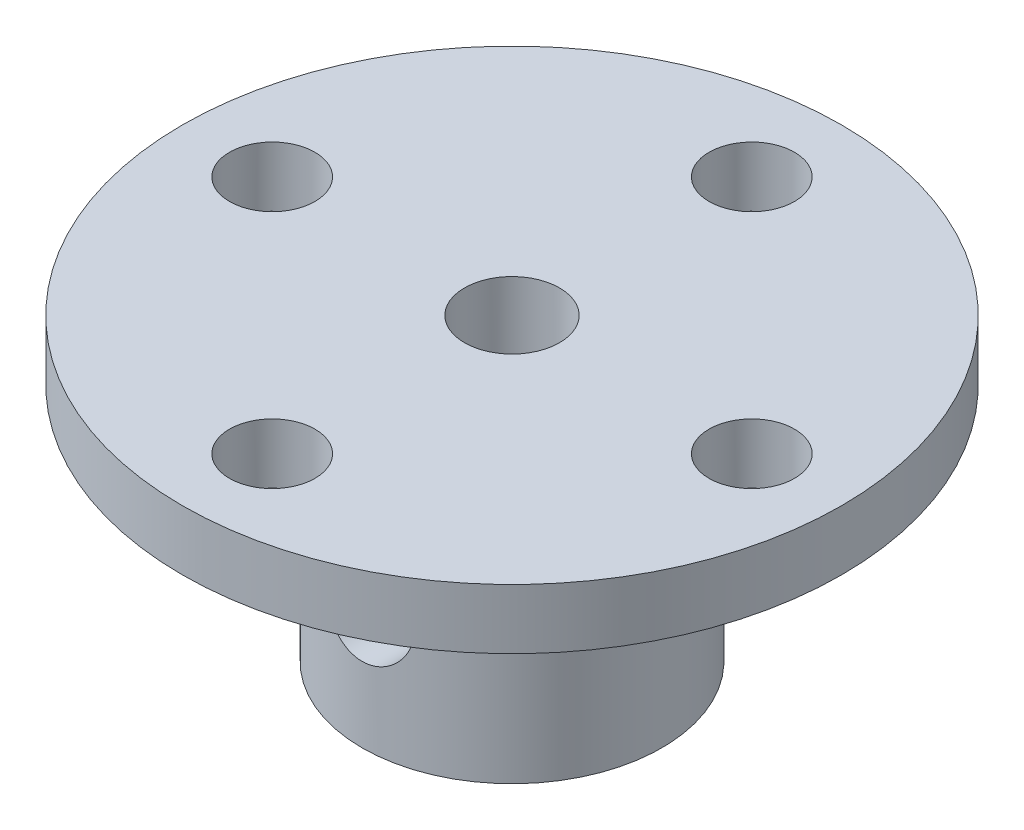
SolidWorks part; units mm, degrees
ref_plane "Front Plane" through (0, 0, 0) normal (0, 0, 1) x (1, 0, 0)
ref_plane "Top Plane" through (0, 0, 0) normal (0, 1, 0) x (1, 0, 0)
ref_plane "Right Plane" through (0, 0, 0) normal (1, 0, 0) x (0, 0, -1)
sketch "Sketch1" plane through (0, 0, 0) normal (0, 1, 0) x (1, 0, 0)
  circle A0 centre (0, 0) radius 11
  dimension "D1" = 22
extrude "Boss-Extrude1" add sketch "Sketch1" along normal blind 2
sketch "Sketch2" plane through (0, 0, 0) normal (0, 1, 0) x (1, 0, 0)
  circle A0 centre (0, 0) radius 5
  dimension "D1" = 10
extrude "Boss-Extrude2" add sketch "Sketch2" against normal blind 8
sketch "Sketch3" plane through (0, 2, 0) normal (0, -1, 0) x (-1, 0, 0)
  circle A0 centre (0, 0) radius 1.585
  dimension "D1" = 3.17
extrude "Cut-Extrude1" cut sketch "Sketch3" along normal through all
sketch "Sketch4" plane through (0, 2, 0) normal (0, 1, 0) x (1, 0, 0)
  circle A0 centre (0, 8) radius 1.425
  dimension "D1" = 2.85
  dimension "D2" = 8
extrude "Cut-Extrude2" cut sketch "Sketch4" against normal up to next
pattern_circular "CirPattern1" count 4 over 360 about axis through (0, 2, 0) along (0, 1, 0) of "Cut-Extrude2"
sketch "Sketch5" plane through (0, 0, 0) normal (0, 0, 1) x (1, 0, 0)
  line L3 (-5, -4) -> (5, -4) construction
  line L4 (-5, 0) -> (-5, -8) construction
  line L5 (5, -8) -> (5, 0) construction
  line L6 (0, 0) -> (0, -8) construction
  line L7 (-5, -8) -> (5, -8) construction
  circle A0 centre (0, -4) radius 1.5
  point P13 (0, -4)
  dimension "D1" = 3
extrude "Cut-Extrude3" cut sketch "Sketch5" against normal through all both and the other way through all
